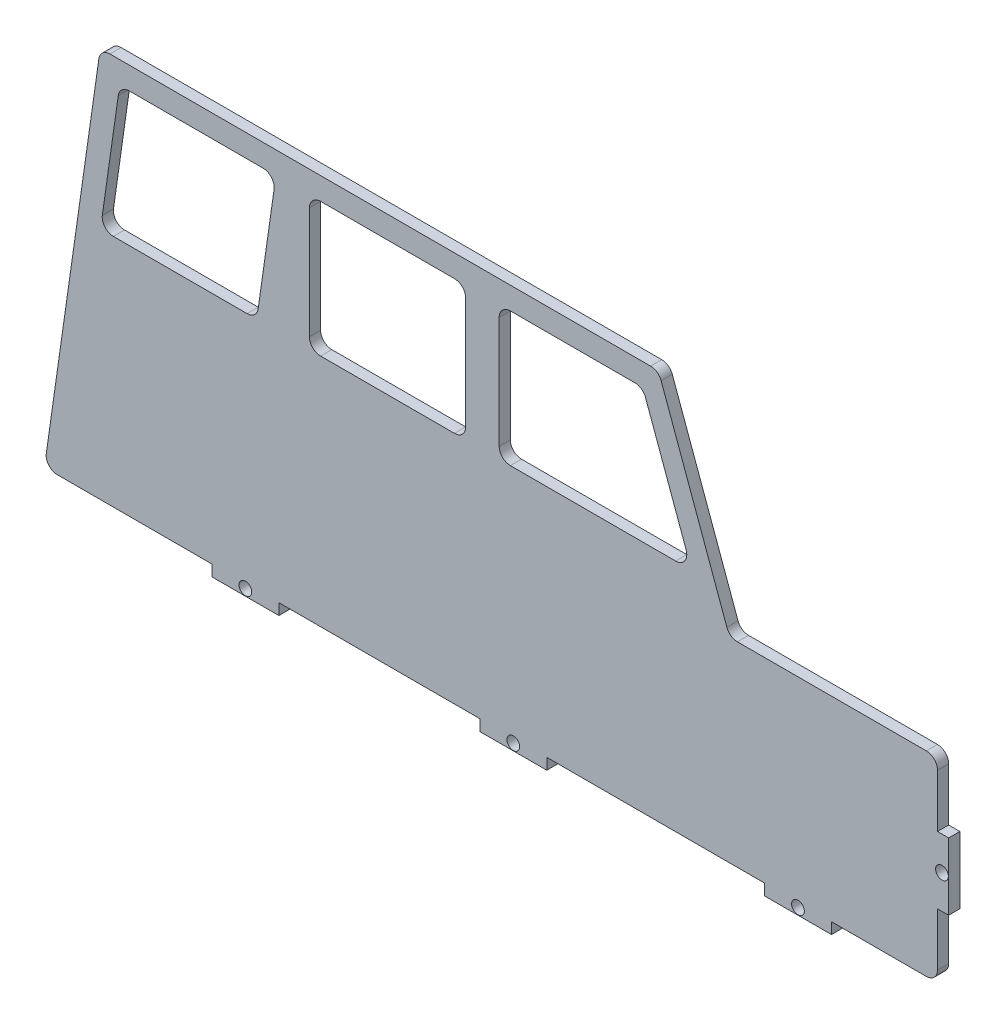
SolidWorks part; units mm, degrees
ref_plane "Front Plane" through (0, 0, 0) normal (0, 0, 1) x (1, 0, 0)
ref_plane "Top Plane" through (0, 0, 0) normal (0, 1, 0) x (1, 0, 0)
ref_plane "Right Plane" through (0, 0, 0) normal (1, 0, 0) x (0, 0, -1)
sketch "Sketch1" plane through (0, 0, 0) normal (0, 0, 1) x (1, 0, 0)
  line L1 (-63.5, 44.45) -> (63.5, 44.45) construction
  line L2 (-63.5, 44.45) -> (-63.5, -44.45) construction
  line L3 (-63.5, -44.45) -> (63.5, -44.45) construction
  line L4 (63.5, 44.45) -> (63.5, -44.45) construction
  line L5 (-63.5, 44.45) -> (63.5, -44.45) construction
  line L6 (-63.5, -44.45) -> (63.5, 44.45) construction
  line L8 (-63.5, 44.45) -> (63.5, 44.45)
  line L13 (-38.1, -44.45) -> (-38.1, -46.99)
  line L14 (-38.1, -46.99) -> (-22.86, -46.99)
  line L15 (-22.86, -46.99) -> (-22.86, -44.45)
  line L16 (22.86, -44.45) -> (22.86, -46.99)
  line L17 (22.86, -46.99) -> (38.1, -46.99)
  line L18 (38.1, -46.99) -> (38.1, -44.45)
  line L19 (87.63, -44.45) -> (87.63, -46.99)
  line L20 (87.63, -46.99) -> (102.87, -46.99)
  line L21 (102.87, -46.99) -> (102.87, -44.45)
  line L22 (-63.5, -44.45) -> (-38.1, -44.45)
  line L23 (-22.86, -44.45) -> (22.86, -44.45)
  line L24 (38.1, -44.45) -> (63.5, -44.45)
  line L25 (63.5, -44.45) -> (87.63, -44.45)
  line L26 (102.87, -44.45) -> (127, -44.45)
  line L27 (-63.5, 44.45) -> (-76.2, -44.45)
  line L28 (-76.2, -44.45) -> (-63.5, -44.45)
  line L29 (63.5, 44.45) -> (79.6785, 0)
  line L30 (79.6785, 0) -> (127, 0)
  line L43 (127, 0) -> (127, -14.605)
  line L44 (127, -14.605) -> (129.54, -14.605)
  line L45 (129.54, -14.605) -> (129.54, -29.845)
  line L46 (129.54, -29.845) -> (127, -29.845)
  line L47 (127, -29.845) -> (127, -44.45)
  point P0 (0, 0)
  dimension "D1" = 88.9
  dimension "D2" = 127
  dimension "D3" = 63.5
  dimension "D4" = 2.54
  dimension "D5" = 15.24
  dimension "D6" = 25.4
  dimension "D7" = 25.4
  dimension "D8" = 24.13
  dimension "D9" = 12.7
  dimension "D10" = 20
  dimension "D11" = 44.45
  dimension "D12" = 14.605
  dimension "D13" = 15.24
  dimension "D14" = 2.54
extrude "Boss-Extrude1" add sketch "Sketch1" along normal blind 2.54
sketch "Sketch2" plane through (0, 0, 2.54) normal (0, 0, 1) x (1, 0, 0)
  line L0 (-59.0941, 39.37) -> (-63.4484, 8.89)
  line L1 (-63.4484, 8.89) -> (-27.8884, 8.89)
  line L2 (-27.8884, 8.89) -> (-23.5341, 39.37)
  line L3 (-23.5341, 39.37) -> (-59.0941, 39.37)
  line L4 (-63.5, 44.45) -> (-76.2, -44.45) construction
  line L5 (27.2659, 39.37) -> (27.2659, 8.89)
  line L6 (-15.9141, 39.37) -> (19.6459, 39.37)
  line L7 (-15.9141, 39.37) -> (-15.9141, 8.89)
  line L8 (-15.9141, 8.89) -> (19.6459, 8.89)
  line L9 (19.6459, 39.37) -> (19.6459, 8.89)
  line L10 (27.2659, 8.89) -> (71.0368, 8.89)
  line L11 (71.0368, 8.89) -> (59.9429, 39.37)
  line L12 (59.9429, 39.37) -> (27.2659, 39.37)
  line L13 (79.6785, 0) -> (63.5, 44.45) construction
  line L14 (63.5, 44.45) -> (-63.5, 44.45) construction
  dimension "D1" = 5.08
  dimension "D2" = 5.08
  dimension "D3" = 7.62
  dimension "D4" = 7.62
  dimension "D5" = 5.08
  dimension "D6" = 30.48
  dimension "D7" = 35.56
  dimension "D8" = 35.56
extrude "Cut-Extrude1" cut sketch "Sketch2" against normal up to next
fillet "Fillet1" radius 2.54 12 edges at (-15.9141, 8.89, 1.27) (19.6459, 8.89, 1.27) (19.6459, 39.37, 1.27) (-15.9141, 39.37, 1.27) (27.2659, 8.89, 1.27) (27.2659, 39.37, 1.27) (-27.8884, 8.89, 1.27) (-23.5341, 39.37, 1.27) (-63.4484, 8.89, 1.27) (-59.0941, 39.37, 1.27) (71.0368, 8.89, 1.27) (59.9429, 39.37, 1.27)
fillet "Fillet3" radius 2.54 6 edges at (79.6785, 0, 1.27) (63.5, 44.45, 1.27) (-63.5, 44.45, 1.27) (-76.2, -44.45, 1.27) (127, -44.45, 1.27) (127, 0, 1.27)
sketch "Sketch4" plane through (0, 0, 2.54) normal (0, 0, 1) x (1, 0, 0)
  line L0 (95.25, -46.99) -> (95.25, -44.45) construction
  line L1 (87.63, -46.99) -> (102.87, -46.99) construction
  line L2 (87.63, -44.45) -> (102.87, -44.45) construction
  line L3 (30.48, -46.99) -> (30.48, -41.3826) construction
  line L4 (22.86, -46.99) -> (38.1, -46.99) construction
  line L5 (-30.48, -46.99) -> (-30.48, -44.0182) construction
  line L6 (-38.1, -46.99) -> (-22.86, -46.99) construction
  line L7 (129.54, -22.225) -> (123.7466, -22.225) construction
  line L8 (129.54, -29.845) -> (129.54, -14.605) construction
  circle A0 centre (95.25, -45.466) radius 1.4478
  circle A1 centre (30.48, -45.466) radius 1.4478
  circle A2 centre (-30.48, -45.466) radius 1.4478
  circle A3 centre (128.016, -22.225) radius 1.4478
  dimension "D1" = 2.8956
  dimension "D3" = 1.524
  dimension "D5" = 1.524
  dimension "D2" = 1.524
  dimension "D4" = 1.524
extrude "Cut-Extrude2" cut sketch "Sketch4" against normal up to next
